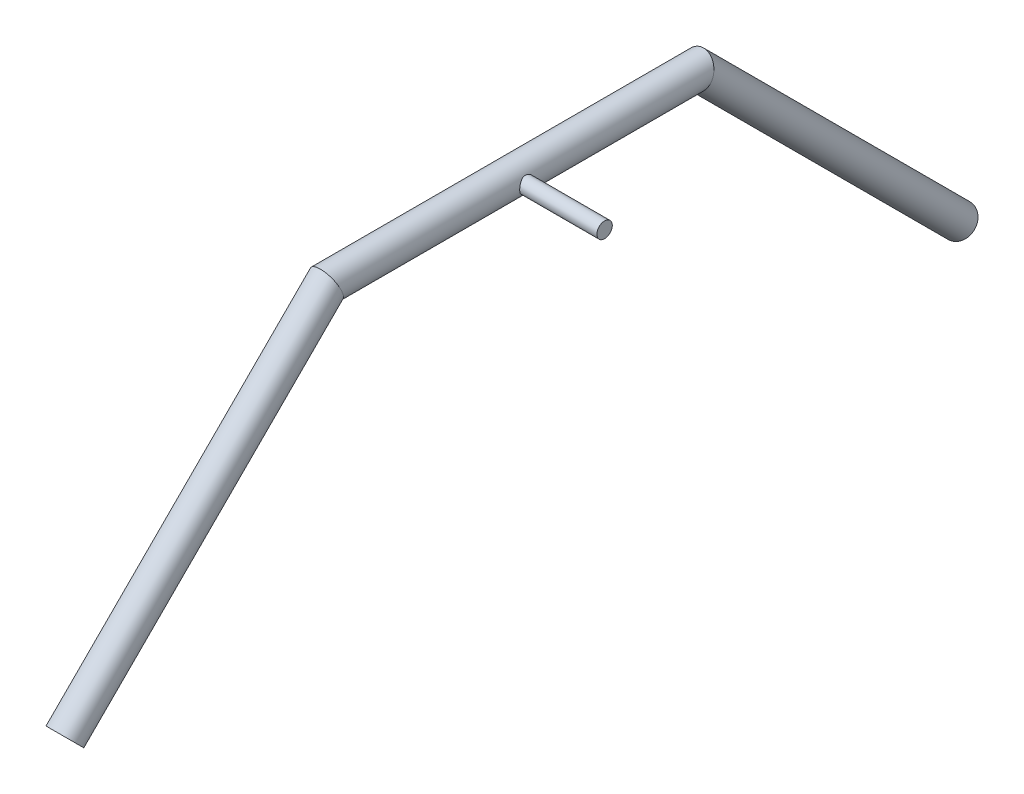
SolidWorks part; units mm, degrees
material "6061 Alloy"
ref_plane "Front Plane" through (0, 0, 0) normal (0, 0, 1) x (1, 0, 0)
ref_plane "Top Plane" through (0, 0, 0) normal (0, 1, 0) x (1, 0, 0)
ref_plane "Right Plane" through (0, 0, 0) normal (1, 0, 0) x (0, 0, -1)
sketch "Sketch2" plane through (0, 0, 0) normal (1, 0, 0) x (0, 0, -1)
  line L0 (-248.1823, -217.0159) -> (-32.6561, -1.4898)
  line L1 (-32.6561, -1.4898) -> (272.1439, -1.4898)
  line L2 (272.1439, -1.4898) -> (487.67, -217.0159)
  dimension "D1" = 135
  dimension "D2" = 135
  dimension "D3" = 304.8
  dimension "D4" = 304.8
  dimension "D5" = 304.8
sweep "Sweep1" add path "Sketch2" circular profile diameter 25.4 parameters "D3"=25.4
sweep "Cut-Sweep1" cut path "Sketch2<2>" circular profile diameter 19.05 parameters "D3"=19.05
sketch "Sketch2<2>" plane through (0, 0, 0) normal (1, 0, 0) x (0, 0, -1) same geometry as "Sketch2"
sketch "Sketch19" plane through (0, 0, 0) normal (1, 0, 0) x (0, 0, -1)
  line L0 (266.8834, -14.1898) -> (266.8834, 11.2102) construction
  line L1 (277.4044, 11.2102) -> (-37.9166, 11.2102) construction
  line L2 (266.8834, 11.2102) -> (-27.3956, -14.1898) construction
  line L3 (-27.3956, -14.1898) -> (-27.3956, 11.2102) construction
  line L4 (-27.3956, 11.2102) -> (266.8834, -14.1898) construction
  circle A0 centre (119.7439, -1.4898) radius 6.35
  dimension "D1" = 12.7
extrude "Boss-Extrude1" add sketch "Sketch19" along normal blind 76.2
equation "\"D2@Sketch2\"=\"D1@Sketch2\""
equation "\"D5@Sketch2\"=\"D4@Sketch2\""
